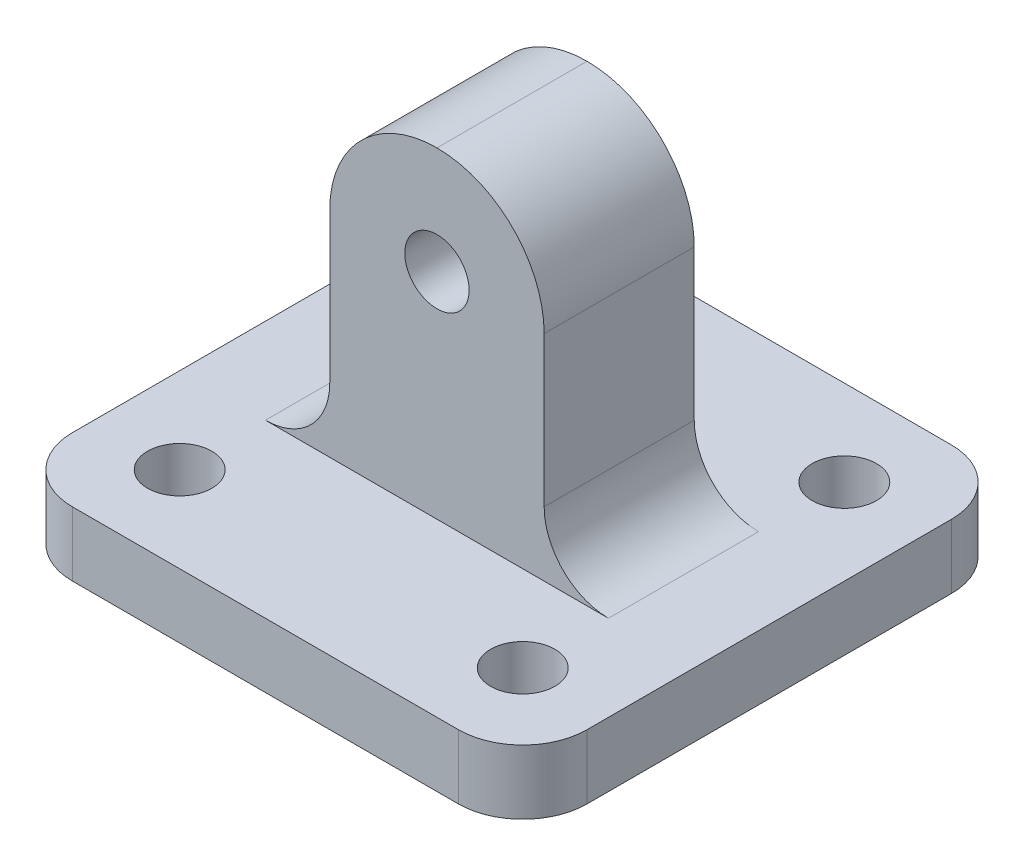
SolidWorks part; units mm, degrees
material "6061 合金"
ref_plane "前视基准面" through (0, 0, 0) normal (0, 0, 1) x (1, 0, 0)
ref_plane "上视基准面" through (0, 0, 0) normal (0, 1, 0) x (1, 0, 0)
ref_plane "右视基准面" through (0, 0, 0) normal (1, 0, 0) x (0, 0, -1)
sketch "草图1" plane through (0, 0, 0) normal (0, 1, 0) x (1, 0, 0)
  line L1 (-12, -11.5) -> (12, -11.5)
  line L2 (-12, -11.5) -> (-12, 11.5)
  line L3 (-12, 11.5) -> (12, 11.5)
  line L4 (12, -11.5) -> (12, 11.5)
  line L5 (-12, -11.5) -> (12, 11.5) construction
  line L6 (-12, 11.5) -> (12, -11.5) construction
  point P0 (0, 0)
  dimension "D1" = 24
  dimension "D2" = 23
extrude "凸台-拉伸1" add sketch "草图1" along normal blind 3
sketch "草图2" plane through (0, 3, 0) normal (0, 1, 0) x (1, 0, 0)
  line L1 (-5, -3.5) -> (5, -3.5)
  line L2 (-5, -3.5) -> (-5, 3.5)
  line L3 (-5, 3.5) -> (5, 3.5)
  line L4 (5, -3.5) -> (5, 3.5)
  line L5 (-5, -3.5) -> (5, 3.5) construction
  line L6 (-5, 3.5) -> (5, -3.5) construction
  point P0 (0, 0)
  dimension "D1" = 7
  dimension "D2" = 10
extrude "凸台-拉伸2" add sketch "草图2" along normal blind 15
sketch "草图3" plane through (0, 0, 3.5) normal (0, 0, 1) x (1, 0, 0)
  line L0 (-5, 18) -> (5, 18) construction
  circle A0 centre (0, 13) radius 1.5
  dimension "D1" = 3
  dimension "D2" = 5
extrude "切除-拉伸2" cut sketch "草图3" against normal through all
sketch "草图4" plane through (0, 3, 0) normal (0, 1, 0) x (1, 0, 0)
  line L1 (-8, -7.5) -> (8, -7.5) construction
  line L2 (-8, -7.5) -> (-8, 7.5) construction
  line L3 (-8, 7.5) -> (8, 7.5) construction
  line L4 (8, -7.5) -> (8, 7.5) construction
  line L5 (-8, -7.5) -> (8, 7.5) construction
  line L6 (-8, 7.5) -> (8, -7.5) construction
  circle A0 centre (-8, 7.5) radius 1.5
  circle A1 centre (-8, -7.5) radius 1.5
  circle A2 centre (8, -7.5) radius 1.5
  circle A3 centre (8, 7.5) radius 1.5
  point P0 (0, 0)
  dimension "D3" = 3
  dimension "D1" = 16
  dimension "D2" = 15
extrude "切除-拉伸3" cut sketch "草图4" against normal through all
fillet "圆角1" radius 5 2 edges at (-5, 18, 0) (5, 18, 0)
fillet "圆角2" radius 3 2 edges at (5, 3, 0) (-5, 3, 0)
fillet "圆角3" radius 3 4 edges at (12, 1.5, -11.5) (12, 1.5, 11.5) (-12, 1.5, 11.5) (-12, 1.5, -11.5)
